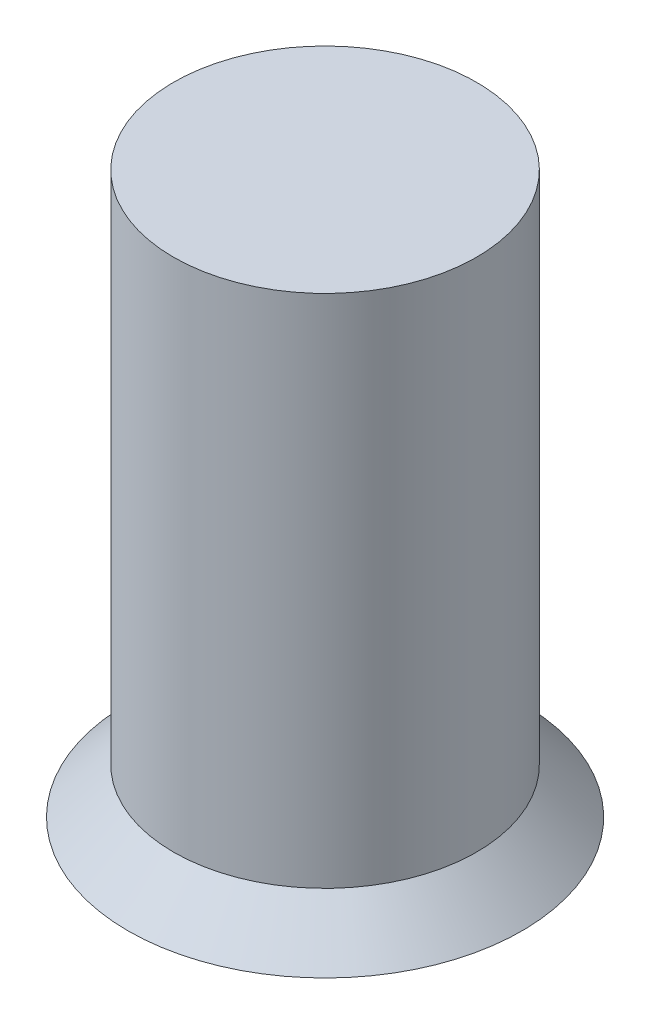
SolidWorks part; units mm, degrees
ref_plane "Plan de face" through (0, 0, 0) normal (0, 0, 1) x (1, 0, 0)
ref_plane "Plan de dessus" through (0, 0, 0) normal (0, 1, 0) x (1, 0, 0)
ref_plane "Plan de droite" through (0, 0, 0) normal (1, 0, 0) x (0, 0, -1)
sketch "Esquisse1" plane through (0, 0, 0) normal (0, 1, 0) x (1, 0, 0)
  circle A0 centre (0, 0) radius 13
extrude "Boss.-Extru.3" add sketch "Esquisse1" along normal blind 3
chamfer "Chanfrein2" distance 3 angle 45 1 edges at (0, 3, 13)
sketch "Esquisse3" plane through (0, 3, 0) normal (0, 1, 0) x (1, 0, 0)
  circle A0 centre (0, 0) radius 10 construction
  circle A1 centre (0, 0) radius 10
extrude "Boss.-Extru.4" add sketch "Esquisse3" along normal blind 34
